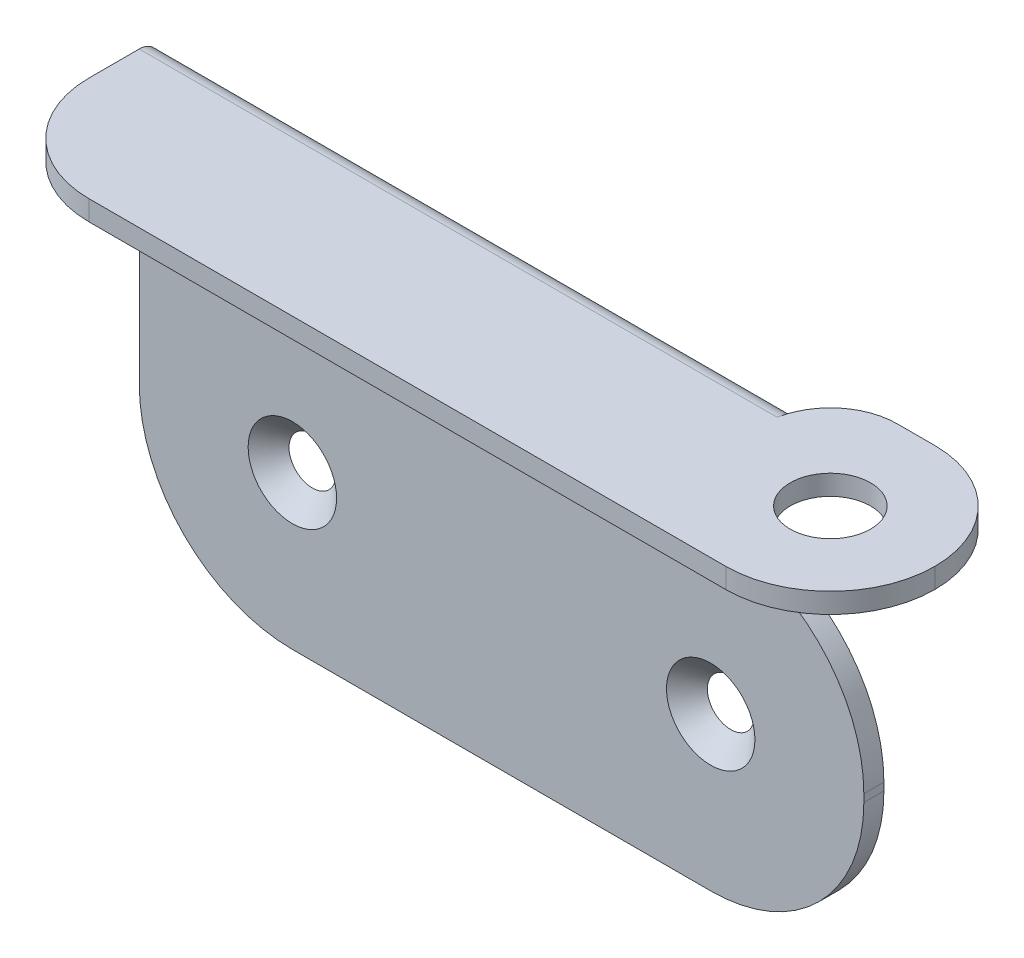
SolidWorks part; units mm, degrees
ref_plane "Front Plane" through (0, 0, 0) normal (0, 0, 1) x (1, 0, 0)
ref_plane "Top Plane" through (0, 0, 0) normal (0, 1, 0) x (1, 0, 0)
ref_plane "Right Plane" through (0, 0, 0) normal (1, 0, 0) x (0, 0, -1)
sketch "Sketch1" plane through (0, 0, 0) normal (0, 0, 1) x (1, 0, 0)
  line L0 (28.7655, 17.1437) -> (28.7655, -21.3844) construction
  line L1 (27.4955, 11.6205) -> (36.703, 20.5105)
  line L2 (36.703, 20.5105) -> (36.703, 22.0345)
  line L4 (-27.4955, 7.4295) -> (-27.4955, -11.6205)
  line L5 (-27.4955, -11.6205) -> (27.4955, -11.6205)
  line L6 (27.4955, 11.6205) -> (27.4955, -11.6205)
  line L7 (36.703, 22.0345) -> (-27.4955, 22.0345)
  line L8 (-27.4955, 22.0345) -> (-27.4955, 7.4295)
  line L9 (0, 27.93) -> (0, -27.9681) construction
  circle A0 centre (15.875, 0) radius 1.778
  circle A1 centre (-15.875, 0) radius 1.778
  point P5 (0, 0)
  dimension "D6" = 3.556
  dimension "D7" = 3.556
  dimension "D2" = 11.6205
  dimension "D3" = 2.54
  dimension "D4" = 1.524
  dimension "D5" = 31.75
  dimension "D8" = 11.6205
  dimension "D9" = 11.6205
  dimension "D10" = 11.6205
  dimension "D11" = 8.89
  dimension "D12" = 7.9375
extrude "Boss-Extrude1" add sketch "Sketch1" along normal blind 1.524
sketch "Sketch2" plane through (0, 0, 1.524) normal (0, 0, 1) x (1, 0, 0)
  line L1 (36.703, 22.0345) -> (17.653, 22.0345)
  line L2 (36.703, 22.0345) -> (36.703, 20.5105)
  line L3 (36.703, 20.5105) -> (17.653, 20.5105)
  line L4 (17.653, 22.0345) -> (17.653, 20.5105)
  dimension "D1" = 19.05
extrude "Boss-Extrude2" add sketch "Sketch2" along normal blind 11.7475
sketch "Sketch3" plane through (0, 20.5105, 0) normal (0, -1, 0) x (1, 0, 0)
  line L0 (27.4955, 1.524) -> (27.4955, 0) construction
  line L1 (17.653, 1.524) -> (36.703, 1.524) construction
  circle A0 centre (28.7655, 5.334) radius 3.048
  dimension "D2" = 6.096
  dimension "D1" = 1.27
  dimension "D3" = 3.81
extrude "Cut-Extrude2" cut sketch "Sketch3" against normal blind 13.9446
sketch "Sketch4" plane through (0, 0, 0) normal (0, 0, -1) x (-1, 0, 0)
  line L0 (-27.4955, -11.6205) -> (-27.4955, 11.6205) construction
  line L1 (-19.8755, 11.6205) -> (-36.703, 11.6205)
  line L2 (-17.3355, 14.1605) -> (-17.3355, 17.9705)
  line L3 (-19.8755, 20.5105) -> (-36.703, 20.5105)
  line L4 (-36.703, 11.6205) -> (-36.703, 20.5105)
  arc A0 (-19.8755, 11.6205) -> (-17.3355, 14.1605) centre (-19.8755, 14.1605) ccw
  arc A1 (-17.3355, 17.9705) -> (-19.8755, 20.5105) centre (-19.8755, 17.9705) ccw
  point P13 (-17.3355, 16.0655)
  dimension "D1" = 2.54
  dimension "D2" = 10.16
extrude "Cut-Extrude3" cut sketch "Sketch4" against normal blind 13.9446
sketch "Sketch5" plane through (0, 0, 1.524) normal (0, 0, 1) x (1, 0, 0)
  line L1 (17.653, 20.5105) -> (-27.4955, 20.5105)
  line L2 (17.653, 20.5105) -> (17.653, 22.0345)
  line L3 (17.653, 22.0345) -> (-27.4955, 22.0345)
  line L4 (-27.4955, 20.5105) -> (-27.4955, 22.0345)
extrude "Boss-Extrude3" add sketch "Sketch5" along normal up to surface (11.7475 mm away) up to face at (27.178, 21.2725, 13.2715)
fillet "Fillet1" radius 7.9375 1 edges at (36.703, 21.2725, 13.2715)
fillet "Fillet3" radius 11.6205 1 edges at (27.4955, -11.6205, 0.762)
fillet "Fillet4" radius 11.6205 2 edges at (-27.4955, -11.6205, 0.762) (27.4955, 11.6205, 0.762)
fillet "Fillet5" radius 1.524 1 edges at (-3.81, 20.5105, 1.524)
fillet "Fillet7" radius 7.9375 1 edges at (-27.4955, 21.2725, 13.2715)
sketch "Sketch6" plane through (0, 0, 0) normal (0, 0, -1) x (-1, 0, 0)
  circle A0 centre (-15.875, 0) radius 1.778
  circle A1 centre (15.875, 0) radius 1.778
  circle A2 centre (-15.875, 0) radius 1.778 construction
  circle A3 centre (15.875, 0) radius 1.778 construction
extrude "Cut-Extrude4" cut sketch "Sketch6" against normal blind 2.54 draft 46 draft outward yes
sketch "Sketch7" plane through (0, 22.0345, 0) normal (0, 1, 0) x (1, 0, 0)
  line L0 (28.7655, 14.656) -> (28.7655, -26.3159) construction
  line L1 (36.703, 0) -> (20.828, 0)
  line L2 (36.703, 0) -> (36.703, 2.6035)
  line L3 (36.703, 2.6035) -> (20.828, 2.6035)
  line L4 (20.828, 0) -> (20.828, 2.6035)
  line L5 (42.4863, -5.334) -> (10.8043, -5.334) construction
  line L6 (28.7655, -13.2715) -> (-19.558, -13.2715) construction
  point P11 (28.7655, -5.334)
extrude "Boss-Extrude4" add sketch "Sketch7" against normal up to surface (1.524 mm away) up to face at (31.8135, 20.5105, 5.334)
fillet "Fillet8" radius 1.524 1 edges at (-3.3337, 22.0345, 0)
fillet "Fillet9" radius 7.9375 1 edges at (36.703, 21.2725, -2.6035)
fillet "Fillet10" radius 5.08 1 edges at (20.828, 21.2725, -2.6035)
